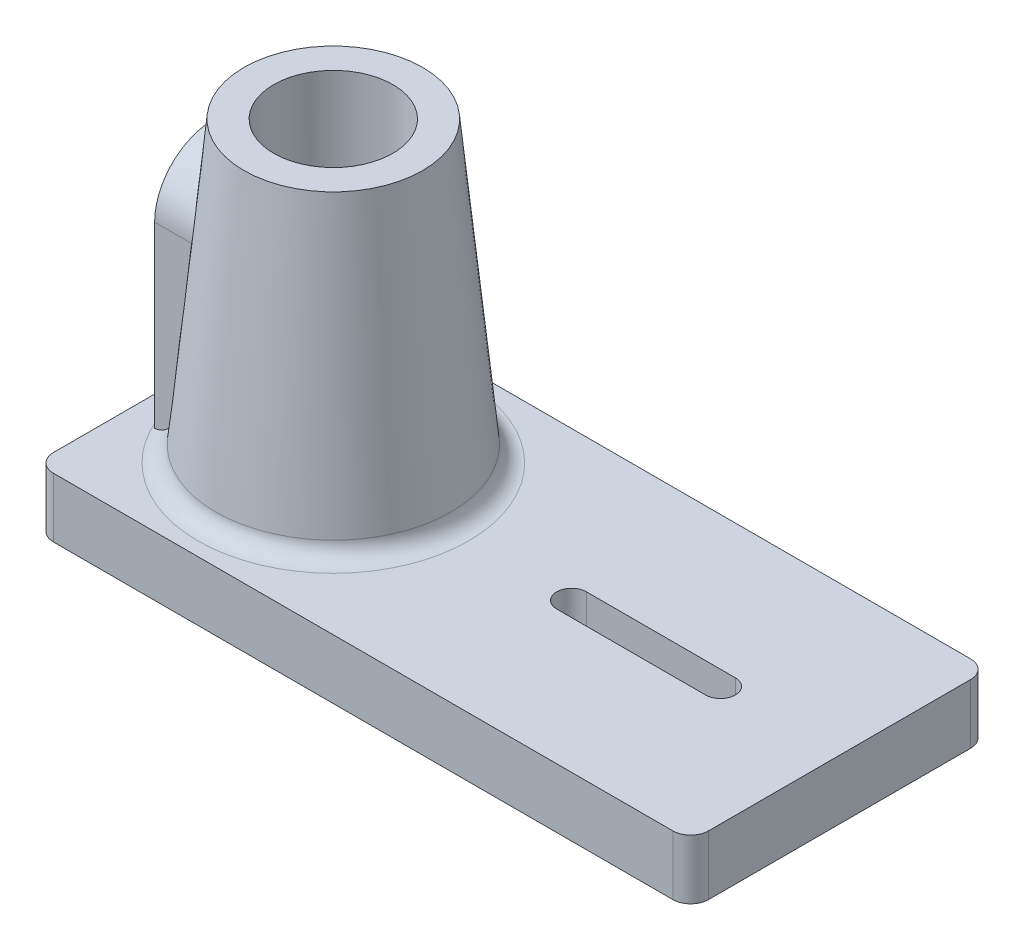
SolidWorks part; units mm, degrees
ref_plane "Front Plane" through (0, 0, 0) normal (0, 0, 1) x (1, 0, 0)
ref_plane "Top Plane" through (0, 0, 0) normal (0, 1, 0) x (1, 0, 0)
ref_plane "Right Plane" through (0, 0, 0) normal (1, 0, 0) x (0, 0, -1)
sketch "Sketch1" plane through (0, 0, 0) normal (0, 1, 0) x (1, 0, 0)
  line L1 (-55, 25) -> (55, 25)
  line L2 (-55, 25) -> (-55, -25)
  line L3 (-55, -25) -> (55, -25)
  line L4 (55, 25) -> (55, -25)
  line L5 (-55, 25) -> (55, -25) construction
  line L6 (-55, -25) -> (55, 25) construction
  line L7 (-55, 0) -> (55, 0) construction
  line L8 (10, 2.5) -> (35, 2.5)
  line L9 (10, -2.5) -> (35, -2.5)
  arc A0 (35, -2.5) -> (35, 2.5) centre (35, 0) ccw
  arc A1 (10, 2.5) -> (10, -2.5) centre (10, 0) ccw
  point P0 (0, 0)
  dimension "D4" = 5
  dimension "D5" = 25
  dimension "D1" = 50
  dimension "D2" = 110
  dimension "D3" = 20
extrude "Boss-Extrude1" add sketch "Sketch1" along normal blind 10
fillet "Fillet1" radius 3 3 edges at (-55, 5, 25) (55, 5, -25) (55, 5, 25) tangent propagation no
fillet "Fillet2" radius 3 1 edges at (-55, 5, -25)
ref_plane "Plane1" through (0, 0, 0) normal (0, 0, 1) x (1, 0, 0)
sketch "Sketch3" plane through (0, 0, 0) normal (0, 0, 1) x (1, 0, 0)
  line L0 (-30, 10) -> (-30, 60) construction
  line L1 (55, 10) -> (55, 0) construction
  line L2 (-52, 10) -> (52, 10) construction
  line L3 (10, 10) -> (7.5, 10) construction
  line L4 (-30, 10) -> (-10, 10)
  line L5 (-30, 60) -> (-15, 60)
  line L6 (-15, 60) -> (-10, 10)
  line L7 (-10, 10) -> (-9.9972, 10.1811)
  line L8 (-30, 10) -> (-30, 60)
  point P4 (8.75, 10)
  point P5 (8.75, 10)
  point P8 (55, 5)
  dimension "D1" = 50
  dimension "D2" = 85
revolve "Revolve1" add sketch "Sketch3" angle 360 about L0 region at (-21.1905, 33.8095, 0)
sketch "Sketch4" plane through (0, 60, 0) normal (0, 1, 0) x (1, 0, 0)
  circle A0 centre (-30, 0) radius 10
extrude "Cut-Extrude1" cut sketch "Sketch4" against normal through all
ref_plane "Plane2" through (-50, 0, 0) normal (-1, 0, 0) x (0, 0, 1)
sketch "Sketch5" plane through (-50, 0, 0) normal (-1, 0, 0) x (0, 0, 1)
  line L0 (-10, 10) -> (10, 10)
  line L2 (10, 10) -> (10, 40)
  line L3 (-10, 10) -> (-10, 40)
  arc A0 (10, 40) -> (-10, 40) centre (0, 40) ccw
extrude "Boss-Extrude2" add sketch "Sketch5" against normal up to surface (2.6795 mm away) up to face at (-10, 10, 0)
sketch "Sketch6" plane through (-50, 0, 0) normal (-1, 0, 0) x (0, 0, 1)
  circle A0 centre (0, 40) radius 5
extrude "Cut-Extrude5" cut sketch "Sketch6" against normal up to next
sketch "Sketch7" plane through (0, 10, 0) normal (0, 1, 0) x (1, 0, 0)
  line L0 (-47.3205, -10) -> (-43.7477, -10) construction
  arc A0 (-47.3205, 10) -> (-47.3205, -10) centre (-30, 0) cw
fillet "Fillet8" radius 3 1 edges at (-10, 10, 0) type face fillet first side face at (-36.767, 27.4999, 0.0233) second side face at (-39.3301, 10, 0)
